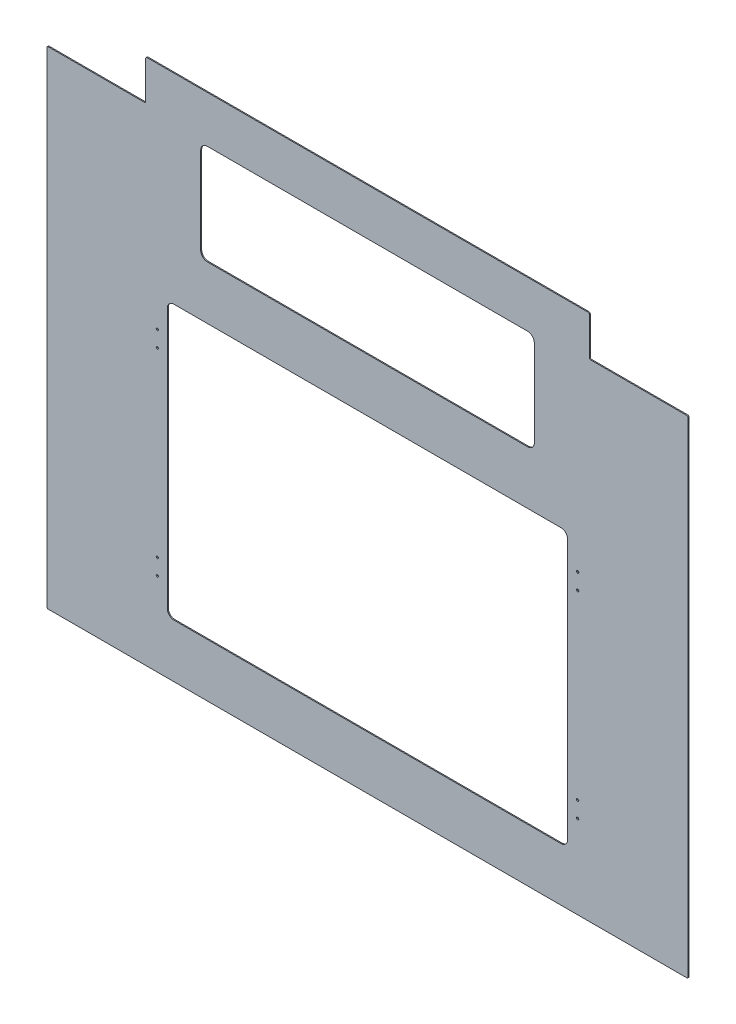
SolidWorks part; units mm, degrees
material "1.0037 (S235JR)"
ref_plane "Front Plane" through (0, 0, 0) normal (0, 0, 1) x (1, 0, 0)
ref_plane "Top Plane" through (0, 0, 0) normal (0, 1, 0) x (1, 0, 0)
ref_plane "Right Plane" through (0, 0, 0) normal (1, 0, 0) x (0, 0, -1)
sketch "Sketch1" plane through (0, 0, 0) normal (0, 0, 1) x (1, 0, 0)
  line L0 (-250, 720) -> (-250, 570)
  line L1 (-480.5, 0) -> (480.5, 0)
  line L2 (-480.5, 0) -> (-480.5, 790)
  line L3 (-480.5, 790) -> (480.5, 790)
  line L4 (480.5, 0) -> (480.5, 790)
  line L6 (-250, 570) -> (250, 570)
  line L7 (0, 790) -> (0, 0) construction
  line L8 (-250, 720) -> (250, 720)
  line L10 (250, 720) -> (250, 570)
  point P13 (0, 570)
  point P15 (0, 720)
  dimension "D1" = 961
  dimension "D2" = 500
  dimension "D3" = 570
  dimension "D5" = 150
  dimension "D6" = 790
base flange "Base-Flange1" sketch "Sketch1" thickness 1.5 reverse thickness direction no parameters "D1"=0.7366
sketch "Sketch2" plane through (0, 0, 0) normal (0, 0, 1) x (1, 0, 0)
  line L1 (-480.5, 790) -> (-332.5, 790)
  line L2 (-480.5, 790) -> (-480.5, 730)
  line L3 (-480.5, 730) -> (-332.5, 730)
  line L4 (-332.5, 790) -> (-332.5, 730)
  dimension "D1" = 148
  dimension "D2" = 60
extrude "Cut-Extrude1" cut sketch "Sketch2" against normal up to next normal cut yes
mirror "Mirror1" about plane through (0, 0, 0) normal (1, 0, 0) of "Cut-Extrude1"
sketch "Sketch3" plane through (0, 0, -1.5) normal (0, 0, -1) x (-1, 0, 0)
  line L0 (0, 0) -> (0, 285) construction
  line L1 (-300, 80) -> (300, 80)
  line L2 (-300, 80) -> (-300, 490)
  line L3 (-300, 490) -> (300, 490)
  line L4 (300, 80) -> (300, 490)
  line L5 (-300, 80) -> (300, 490) construction
  line L6 (-300, 490) -> (300, 80) construction
  line L7 (480.5, 0) -> (-480.5, 0) construction
  point P0 (0, 285)
  dimension "D1" = 80
  dimension "D2" = 600
  dimension "D3" = 410
extrude "Cut-Extrude2" cut sketch "Sketch3" against normal up to next normal cut yes
hole_wizard "M3 Clearance Hole1" positions "Sketch4" profile "Sketch5" hole size "M3" standard "DIN" end condition up to next
sketch "Sketch4" plane through (0, 0, -1.5) normal (0, 0, -1) x (-1, 0, 0)
  line L0 (-300, 490) -> (-300, 80) construction
  line L1 (-300, 285) -> (300, 285) construction
  line L2 (300, 80) -> (300, 490) construction
  line L4 (-300, 80) -> (300, 80) construction
  point P0 (-315, 125)
  point P2 (-315, 149)
  point P13 (-315, 445)
  point P14 (-315, 421)
  dimension "D1" = 24
  dimension "D2" = 15
  dimension "D3" = 45
sketch "Sketch5" plane through (315, 125, -1.5) normal (1, 0, 0) x (0, 1, 0)
  line L0 (0, 0) -> (0, 1.5)
  line L1 (0, 1.5) -> (1.7, 1.5)
  line L2 (1.7, 1.5) -> (1.7, 0)
  line L5 (1.7, 0) -> (0, 0)
  line L11 (0, -6.35) -> (0, 107.95) construction
  dimension "Thru Hole Dia." = 3.4
  dimension "Thru Hole Depth" = 1.5
mirror "Mirror2" about plane through (0, 0, 0) normal (1, 0, 0) of "M3 Clearance Hole1"
fillet "Fillet1" radius 10 8 edges at (-250, 570, -0.75) (-250, 720, -0.75) (250, 720, -0.75) (250, 570, -0.75) (-300, 80, -0.75) (-300, 490, -0.75) (300, 490, -0.75) (300, 80, -0.75)
fillet "Fillet2" radius 2 8 edges at (-480.5, 0, -0.75) (480.5, 0, -0.75) (480.5, 730, -0.75) (-480.5, 730, -0.75) (-332.5, 790, -0.75) (-332.5, 730, -0.75) (332.5, 790, -0.75) (332.5, 730, -0.75)
sketch "Bend-Lines1" [suppressed] plane through (0, 0, 0) normal (0, 1, 0) x (1, 0, 0)
sketch "Bounding-Box1" [suppressed] plane through (0, 0, 0) normal (0, 1, 0) x (1, 0, 0)
sheet metal parameters "Sheet-Metal1" thickness 1.5 parameters "D1"=0.7366
flat pattern "Flat-Pattern1" [suppressed]
sketch "Bend-Lines2" plane through (0, 0, 0) normal (0, 1, 0) x (1, 0, 0)
sketch3d "Bounding-Box2" [suppressed]
  line L0 (0, 0, 0) -> (958, 0, 0) construction
  line L1 (0, 740, 0) -> (958, 740, 0) construction
  line L2 (0, 0, 0) -> (0, 740, 0) construction
  line L3 (958, 0, 0) -> (958, 740, 0) construction
sheet metal parameters "Sheet-Metal2" thickness 1.5 parameters "D1"=0.7366
flat pattern "Flat-Pattern1"
sketch "Bend-Lines2" plane through (0, 0, 0) normal (0, 1, 0) x (1, 0, 0)
sketch3d "Bounding-Box2" [suppressed]
  line L0 (-479, 0, 0) -> (479, 0, 0) construction
  line L1 (-479, 740, 0) -> (479, 740, 0) construction
  line L2 (-479, 0, 0) -> (-479, 740, 0) construction
  line L3 (479, 0, 0) -> (479, 740, 0) construction
sheet metal parameters "Sheet-Metal3" thickness 1.5 parameters "D1"=0.7366
flat pattern "Flat-Pattern1"
sketch "Bend-Lines2" plane through (0, 0, 0) normal (0, 1, 0) x (1, 0, 0)
sketch3d "Bounding-Box2" [suppressed]
  line L0 (-479, 0, 0) -> (479, 0, 0) construction
  line L1 (-479, 740, 0) -> (479, 740, 0) construction
  line L2 (-479, 0, 0) -> (-479, 740, 0) construction
  line L3 (479, 0, 0) -> (479, 740, 0) construction
sheet metal parameters "Sheet-Metal4" thickness 1.5 parameters "D1"=0.7366
flat pattern "Flat-Pattern1"
sketch "Bend-Lines2" plane through (0, 0, 0) normal (0, 1, 0) x (1, 0, 0)
sketch3d "Bounding-Box2" [suppressed]
  line L0 (-480.5, 0, 0) -> (480.5, 0, 0) construction
  line L1 (-480.5, 740, 0) -> (480.5, 740, 0) construction
  line L2 (-480.5, 0, 0) -> (-480.5, 740, 0) construction
  line L3 (480.5, 0, 0) -> (480.5, 740, 0) construction
sheet metal parameters "Sheet-Metal5" thickness 1.5 parameters "D1"=0.7366
flat pattern "Flat-Pattern1"
sketch "Bend-Lines2" plane through (0, 0, 0) normal (0, 1, 0) x (1, 0, 0)
sketch3d "Bounding-Box2" [suppressed]
  line L0 (-480.5, 0, 0) -> (480.5, 0, 0) construction
  line L1 (-480.5, 740, 0) -> (480.5, 740, 0) construction
  line L2 (-480.5, 0, 0) -> (-480.5, 740, 0) construction
  line L3 (480.5, 0, 0) -> (480.5, 740, 0) construction
sheet metal parameters "Sheet-Metal6" thickness 1.5 parameters "D1"=0.7366
flat pattern "Flat-Pattern1"
sketch "Bend-Lines2" plane through (0, 0, 0) normal (0, 1, 0) x (1, 0, 0)
sketch3d "Bounding-Box2" [suppressed]
  line L0 (-480.4996, 790.0004, 0) -> (480.5, 789.9999, 0) construction
  line L1 (-480.5, 0.0005, 0) -> (480.4996, 0, 0) construction
  line L2 (-480.4996, 790.0004, 0) -> (-480.5, 0.0005, 0) construction
  line L3 (480.5, 789.9999, 0) -> (480.4996, 0, 0) construction
